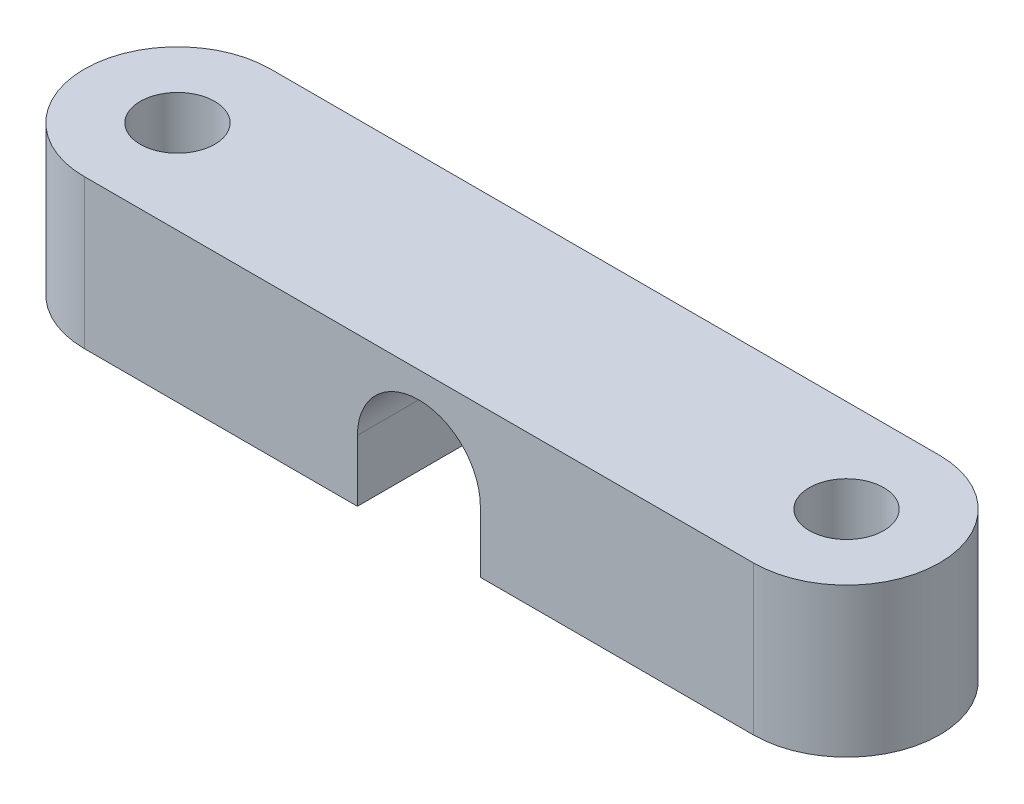
SolidWorks part; units mm, degrees
ref_plane "Front Plane" through (0, 0, 0) normal (0, 0, 1) x (1, 0, 0)
ref_plane "Top Plane" through (0, 0, 0) normal (0, 1, 0) x (1, 0, 0)
ref_plane "Right Plane" through (0, 0, 0) normal (1, 0, 0) x (0, 0, -1)
sketch "Sketch1" plane through (0, 0, 0) normal (0, 1, 0) x (1, 0, 0)
  line L0 (-17.9605, 17.9605) -> (17.9605, -17.9605) construction
  line L1 (-17.9605, 22.9605) -> (17.9605, 22.9605)
  line L2 (17.9605, 17.9605) -> (-17.9605, -17.9605) construction
  line L4 (-17.9605, 12.9605) -> (17.9605, 12.9605)
  circle A0 centre (-17.9605, 17.9605) radius 2
  circle A1 centre (17.9605, 17.9605) radius 2
  arc A2 (-17.9605, 22.9605) -> (-17.9605, 12.9605) centre (-17.9605, 17.9605) ccw
  arc A3 (17.9605, 12.9605) -> (17.9605, 22.9605) centre (17.9605, 17.9605) ccw
  point P2 (0, 0)
  point P5 (0, 0)
  dimension "D2" = 4
  dimension "D3" = 10
  dimension "D1" = 50.8
extrude "Boss-Extrude1" add sketch "Sketch1" along normal blind 8
sketch "Sketch2" plane through (0, 0, -12.9605) normal (0, 0, 1) x (1, 0, 0)
  line L0 (0, 3.3) -> (0, 0) construction
  line L1 (-3.3, 3.3) -> (-3.3, 0)
  line L2 (-17.9605, 0) -> (17.9605, 0) construction
  line L4 (3.3, 3.3) -> (3.3, 0)
  line L5 (-3.42, 0) -> (3.3, 0)
  arc A0 (3.3, 3.3) -> (-3.3, 3.3) centre (0, 3.3) ccw
  line M4 (-17.9605, 0) -> (17.9605, 0)
  dimension "D1" = 6.6
  dimension "D2" = 3.3
extrude "Cut-Extrude1" cut sketch "Sketch2" against normal through all contours L4 A0 L1 L5 M4 region at (0, 2.9919, -12.9605)
